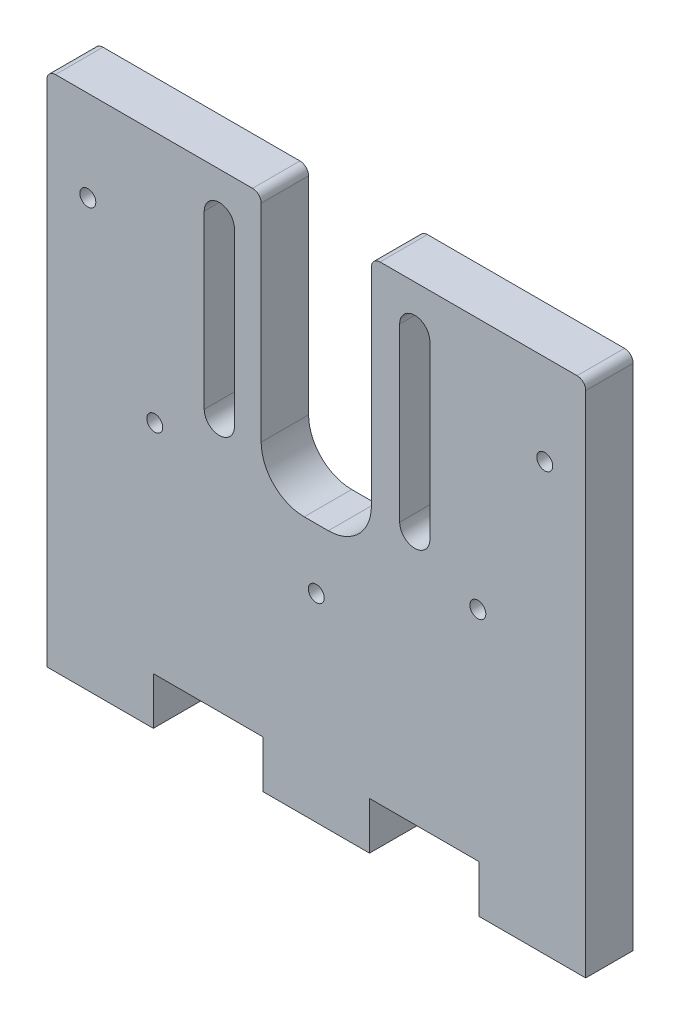
SolidWorks part; units mm, degrees
ref_plane "Front Plane" through (0, 0, 0) normal (0, 0, 1) x (1, 0, 0)
ref_plane "Top Plane" through (0, 0, 0) normal (0, 1, 0) x (1, 0, 0)
ref_plane "Right Plane" through (0, 0, 0) normal (1, 0, 0) x (0, 0, -1)
sketch "Sketch2" plane through (0, 0, 0) normal (0, 0, 1) x (1, 0, 0)
  line L1 (-0.1872, 0) -> (-0.1872, 118)
  line L9 (1.8128, 120) -> (47.5254, 120)
  line L10 (49.5254, 118) -> (49.5254, 70)
  line L11 (59.5254, 60) -> (65.1001, 60)
  line L12 (75.1001, 70) -> (75.1001, 118)
  line L13 (77.1001, 120) -> (122.8128, 120)
  line L14 (124.8128, 118) -> (124.8128, 0)
  line L16 (39.8128, 70) -> (39.8128, 109.8096) construction
  line L17 (36.3128, 70) -> (36.3128, 109.8096)
  line L18 (43.3128, 70) -> (43.3128, 109.8096)
  line L19 (-0.1872, 0) -> (24.5128, 0)
  line L20 (85.1566, 70) -> (85.1566, 109.8096) construction
  line L21 (88.6566, 70) -> (88.6566, 109.8096)
  line L22 (81.6566, 70) -> (81.6566, 109.8096)
  line L23 (24.5128, 0) -> (24.5128, 11)
  line L24 (24.5128, 11) -> (49.9628, 11)
  line L25 (49.9628, 11) -> (49.9628, 0)
  line L26 (49.9628, 0) -> (74.6628, 0)
  line L27 (74.6628, 0) -> (74.6628, 11)
  line L28 (74.6628, 11) -> (100.1128, 11)
  line L29 (100.1128, 11) -> (100.1128, 0)
  line L30 (100.1128, 0) -> (124.8128, 0)
  line L32 (49.5254, 60) -> (75.1001, 60) construction
  line L33 (49.5254, 60) -> (49.5254, 138) construction
  line L34 (49.5254, 138) -> (75.1001, 138) construction
  line L35 (75.1001, 60) -> (75.1001, 138) construction
  line L36 (49.5254, 60) -> (75.1001, 138) construction
  line L37 (49.5254, 138) -> (75.1001, 60) construction
  arc A6 (59.5254, 60) -> (49.5254, 70) centre (59.5254, 70) cw
  arc A7 (65.1001, 60) -> (75.1001, 70) centre (65.1001, 70) ccw
  arc A8 (49.5254, 118) -> (47.5254, 120) centre (47.5254, 118) ccw
  arc A9 (77.1001, 120) -> (75.1001, 118) centre (77.1001, 118) ccw
  arc A10 (1.8128, 120) -> (-0.1872, 118) centre (1.8128, 118) ccw
  arc A11 (124.8128, 118) -> (122.8128, 120) centre (122.8128, 118) ccw
  arc A14 (36.3128, 70) -> (43.3128, 70) centre (39.8128, 70) ccw
  arc A15 (43.3128, 109.8096) -> (36.3128, 109.8096) centre (39.8128, 109.8096) ccw
  arc A16 (88.6566, 70) -> (81.6566, 70) centre (85.1566, 70) cw
  arc A17 (81.6566, 109.8096) -> (88.6566, 109.8096) centre (85.1566, 109.8096) cw
  circle A23 centre (62.3128, 99) radius 53 construction
  circle A24 centre (62.3128, 46) radius 1.85
  circle A25 centre (24.8361, 61.5233) radius 1.85
  circle A26 centre (9.3128, 99) radius 1.85
  circle A27 centre (24.8361, 136.4767) radius 1.85 [skipped]
  circle A28 centre (62.3128, 152) radius 1.85 [skipped]
  circle A29 centre (99.7894, 136.4767) radius 1.85 [skipped]
  circle A30 centre (115.3128, 99) radius 1.85
  circle A31 centre (99.7894, 61.5233) radius 1.85
  point P24 (39.8128, 89.9048)
  point P32 (85.1566, 89.9048)
  point P45 (62.3128, 99)
  point P69 (62.3128, 99)
  dimension "D1" = 125
  dimension "D2" = 120
  dimension "D3" = 2
  dimension "D4" = 2
  dimension "D5" = 2
  dimension "D6" = 2
  dimension "D8" = 106
  dimension "D7" = 11
  dimension "D9" = 3.7
  dimension "D10" = 8
  dimension "D11" = 24.7
extrude "Boss-Extrude7" add sketch "Sketch2" along normal blind 11
